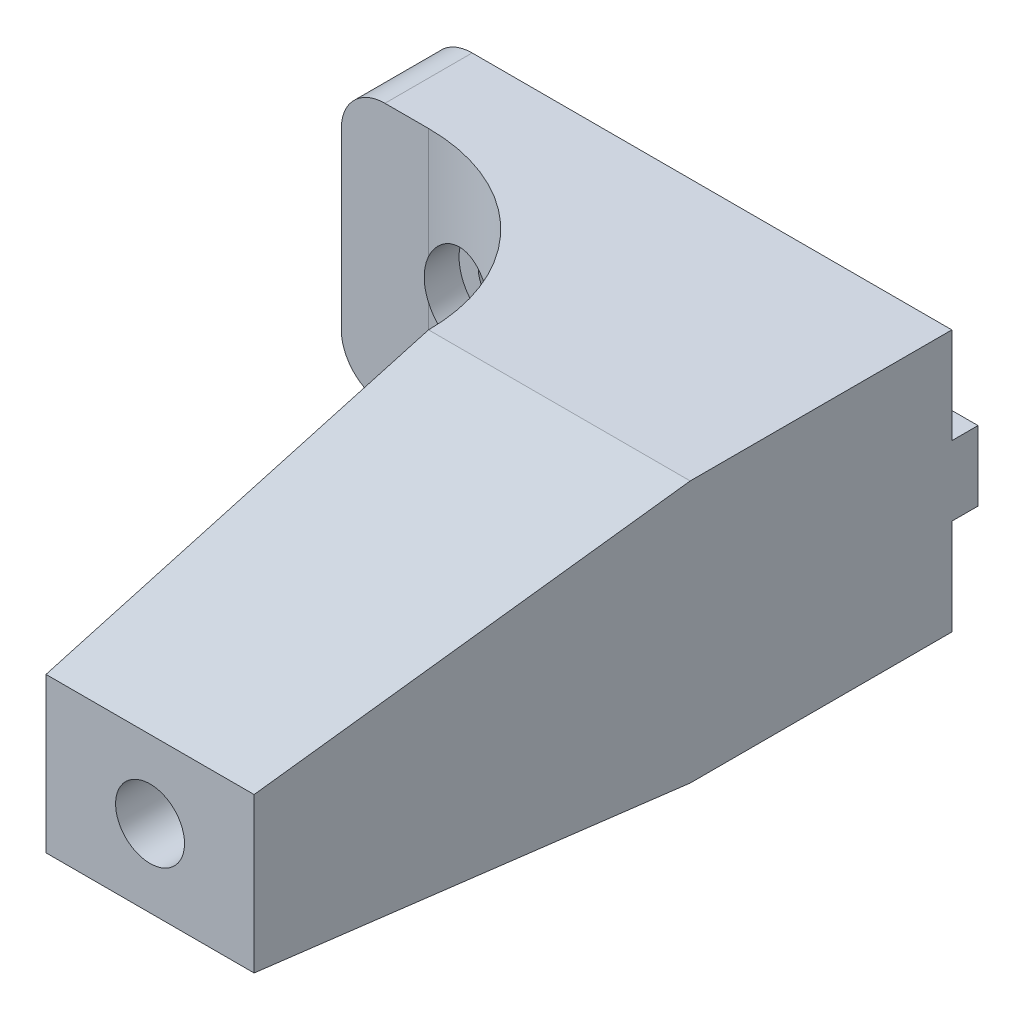
SolidWorks part; units mm, degrees
ref_plane "Přední rovina" through (0, 0, 0) normal (0, 0, 1) x (1, 0, 0)
ref_plane "Horní rovina" through (0, 0, 0) normal (0, 1, 0) x (1, 0, 0)
ref_plane "Pravá rovina" through (0, 0, 0) normal (1, 0, 0) x (0, 0, -1)
sketch "Base sketch" plane through (0, 0, 0) normal (0, 0, 1) x (1, 0, 0)
  line L1 (-30, 15) -> (30, 15)
  line L2 (-30, 15) -> (-30, -15)
  line L3 (-30, -15) -> (30, -15)
  line L4 (30, 15) -> (30, -15)
  line L5 (-30, 15) -> (30, -15) construction
  line L6 (-30, -15) -> (30, 15) construction
  point P0 (0, 0)
  dimension "D1" = 60
  dimension "D2" = 30
extrude "Base" add sketch "Base sketch" along normal blind 10
sketch "Tower sketch" plane through (0, 0, 10) normal (0, 0, 1) x (1, 0, 0)
  line L0 (30, -15) -> (30, 15) construction
  line L1 (30, 15) -> (0, 15)
  line L2 (30, 15) -> (30, -15)
  line L3 (30, -15) -> (0, -15)
  line L4 (0, 15) -> (0, -15)
  line L5 (30, 15) -> (-30, 15) construction
  line L6 (-30, -15) -> (30, -15) construction
extrude "Tower" add sketch "Tower sketch" along normal blind 70
fillet "Base radius" radius 20 1 edges at (0, 0, 10)
sketch "Base screw sketch" plane through (0, 0, 10) normal (0, 0, 1) x (1, 0, 0)
  line L0 (-30, 0) -> (0, 0)
  line L1 (-30, 15) -> (-30, -15) construction
  point P5 (-15, 0)
  dimension "D1" = 15
ref_plane "Rovina1" through (0, 0, 30) normal (0, 0, 1) x (1, 0, 0)
hole_wizard "Base screw" positions "Skica7" profile "Skica8" counterbore size "M6" standard "ISO" end condition up to next
sketch "Skica7" plane through (0, 0, 30) normal (0, 0, 1) x (1, 0, 0)
  point P0 (-15, 0)
sketch "Skica8" plane through (-15, 0, 30) normal (1, 0, 0) x (0, -1, 0)
  line L0 (0, 0) -> (0, 30)
  line L1 (0, 30) -> (3.3, 30)
  line L3 (3.3, 30) -> (3.3, 24)
  line L4 (3.3, 24) -> (5.5, 24)
  line L5 (5.5, 24) -> (5.5, 0)
  line L7 (5.5, 0) -> (0, 0)
  line L11 (0, -6.35) -> (0, 107.95) construction
  dimension "Průměr díry skrz" = 6.6
  dimension "Hloubka díry skrz" = 30
  dimension "Průměr válcového zahloubení" = 11
  dimension "Hloubka válcového zahloubení" = 24
chamfer "tower bevel" distance 50 angle 7 3 edges at (0, 0, 80) (15, 15, 80) (15, -15, 80) first distance on face at (0, 0, 55) first distance on face at (-2.2654, 15, 29.4083) first distance on face at (-2.2654, -15, 29.4083)
sketch "Top cover screw hole sketch" plane through (0, 0, 80) normal (0, 0, 1) x (1, 0, 0)
  line L0 (18.0696, 8.8608) -> (18.0696, -8.8608)
  line L3 (30, 8.8608) -> (6.1392, 8.8608) construction
  line L4 (6.1392, -8.8608) -> (30, -8.8608) construction
  circle A0 centre (18.0696, 0) radius 3.95
  point P8 (18.0696, 0)
  dimension "D1" = 7.9
extrude "Cover srew hole" cut sketch "Top cover screw hole sketch" against normal blind 15 contours A0
sketch "profile sketch" plane through (0, 0, 0) normal (0, 0, -1) x (-1, 0, 0)
  line L0 (30, 15) -> (30, -15) construction
  line L1 (-30, 4) -> (30, 4)
  line L2 (-30, 4) -> (-30, -4)
  line L3 (-30, -4) -> (30, -4)
  line L4 (30, 4) -> (30, -4)
  line L5 (-30, 4) -> (30, -4) construction
  line L6 (-30, -4) -> (30, 4) construction
  circle A0 centre (15, 0) radius 8
  point P0 (0, 0)
  line M3 (-30, 15) -> (-30, -15)
  line M5 (30, -15) -> (30, 15)
  dimension "D2" = 16
  dimension "D1" = 8
extrude "Přidat vysunutím3" add sketch "profile sketch" along normal blind 3 contours A0 L1 L3 M3 | A0 L3 L1 M5 region at (11.3251, 0, 0) region at (-26.3196, 0, 0)
chamfer "Profile bevel" distance 3 angle 45 1 edges at (-23, 0, -3)
fillet "rounding" radius 5 2 edges at (-30, 15, 5) (-30, -15, 5)
